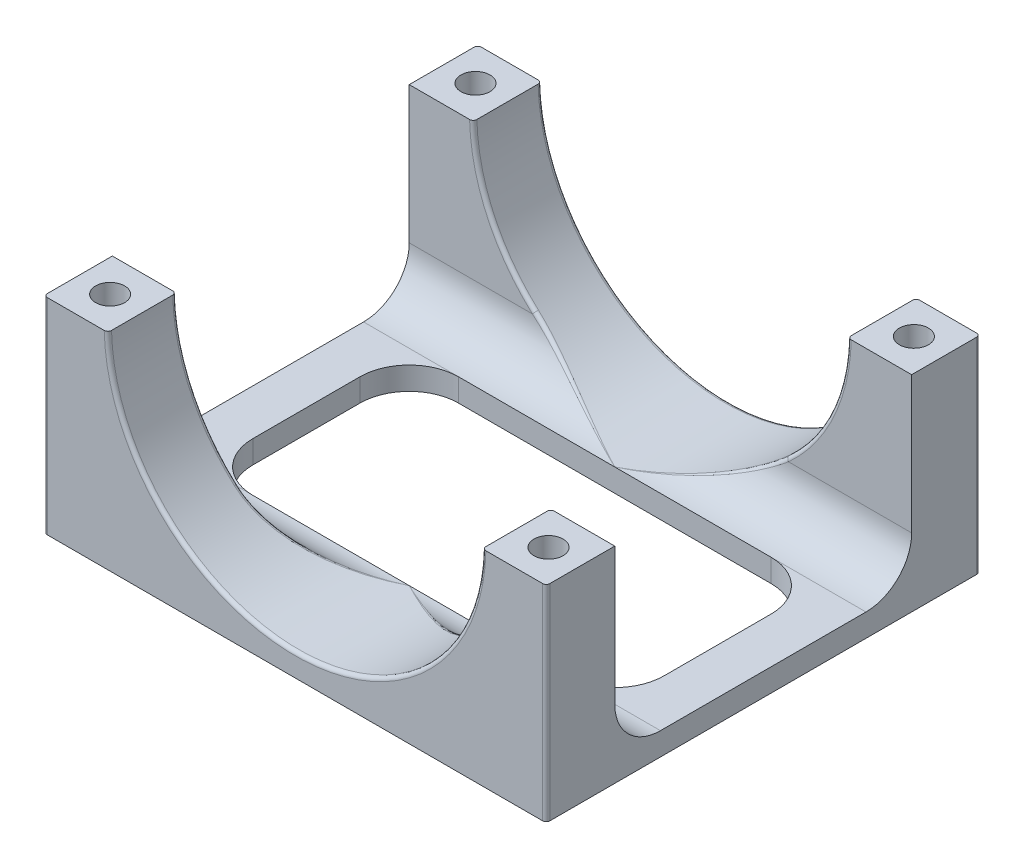
SolidWorks part; units mm, degrees
material "6061-T6 (SS)"
ref_plane "Front Plane" through (0, 0, 0) normal (0, 0, 1) x (1, 0, 0)
ref_plane "Top Plane" through (0, 0, 0) normal (0, 1, 0) x (1, 0, 0)
ref_plane "Right Plane" through (0, 0, 0) normal (1, 0, 0) x (0, 0, -1)
sketch "Sketch1" plane through (0, 0, 0) normal (0, 0, 1) x (1, 0, 0)
  line L0 (-1000, 0) -> (49000, 0) construction
  line L1 (-34.925, -0.635) -> (-26.0273, -0.635)
  line L2 (-34.925, -0.635) -> (-34.925, -29.21)
  line L3 (-34.925, -29.21) -> (34.925, -29.21)
  line L4 (34.925, -29.21) -> (34.925, -0.635)
  line L5 (34.925, -0.635) -> (26.0273, -0.635)
  arc A0 (-26.0273, -0.635) -> (26.0273, -0.635) centre (0, 0) ccw
  dimension "D1" = 52.07
  dimension "D2" = 1.27
  dimension "D3" = 69.85
  dimension "D4" = 3.175
extrude "Boss-Extrude1" add sketch "Sketch1" along normal mid plane 60.325
sketch "Sketch3" plane through (34.925, 0, 0) normal (1, 0, 0) x (0, 0, -1)
  line L0 (-30.1625, -29.21) -> (30.1625, -29.21) construction
  line L1 (-20.6375, 26.035) -> (20.6375, 26.035)
  line L2 (-20.6375, 26.035) -> (-20.6375, -19.685)
  line L3 (-14.2875, -26.035) -> (14.2875, -26.035)
  line L4 (20.6375, 26.035) -> (20.6375, -19.685)
  line L5 (-20.6375, 26.035) -> (20.6375, -26.035) construction
  line L6 (-20.6375, -26.035) -> (20.6375, 26.035) construction
  line L7 (30.1625, -29.21) -> (30.1625, -0.635) construction
  arc A0 (-20.6375, -19.685) -> (-14.2875, -26.035) centre (-14.2875, -19.685) ccw
  arc A1 (14.2875, -26.035) -> (20.6375, -19.685) centre (14.2875, -19.685) ccw
  point P0 (0, 0)
  dimension "D3" = 6.35
  dimension "D1" = 3.175
  dimension "D2" = 9.525
extrude "Cut-Extrude2" cut sketch "Sketch3" against normal through all
sketch "Sketch4" plane through (0, -26.035, 0) normal (0, 1, 0) x (1, 0, 0)
  line L0 (-34.925, 14.2875) -> (0, 14.2875) construction
  line L1 (-28.575, 14.2875) -> (28.575, 14.2875)
  line L2 (-28.575, 14.2875) -> (-28.575, -14.2875)
  line L3 (-28.575, -14.2875) -> (28.575, -14.2875)
  line L4 (28.575, 14.2875) -> (28.575, -14.2875)
  line L5 (-28.575, 14.2875) -> (28.575, -14.2875) construction
  line L6 (-28.575, -14.2875) -> (28.575, 14.2875) construction
  line L7 (-34.925, -14.2875) -> (-34.925, 14.2875) construction
  point P0 (0, 0)
  dimension "D1" = 6.35
extrude "Cut-Extrude3" cut sketch "Sketch4" against normal through all
fillet "Fillet1" radius 6.858 4 edges at (-28.575, -27.6225, 14.2875) (28.575, -27.6225, 14.2875) (28.575, -27.6225, -14.2875) (-28.575, -27.6225, -14.2875)
hole_wizard "#10-32 Tapped Hole1" positions "Sketch5" profile "Sketch6" tap size "#10-32" standard "ANSI Inch" end condition through all
sketch "Sketch5" plane through (0, -0.635, 0) normal (0, 1, 0) x (1, 0, 0)
  line L0 (-30.4761, 25.4) -> (30.4761, -25.4)
  line L3 (30.4761, 25.4) -> (-30.4761, -25.4)
  line L5 (-34.925, -25.4) -> (-26.0273, -25.4)
  line L6 (-34.925, -30.1625) -> (-34.925, -20.6375) construction
  line L7 (-26.0273, -30.1625) -> (-26.0273, -20.6375) construction
  point P0 (-30.4761, 25.4)
  point P2 (-30.4761, -25.4)
  point P4 (30.4761, 25.4)
  point P6 (30.4761, -25.4)
  dimension "D1" = 50.8
sketch "Sketch6" plane through (-30.4761, -0.635, -25.4) normal (1, 0, 0) x (0, 0, 1)
  line L0 (0, 0) -> (0, 28.575)
  line L1 (0, 28.575) -> (2.0193, 28.575)
  line L2 (2.0193, 28.575) -> (2.0193, 0)
  line L5 (2.0193, 0) -> (0, 0)
  line L11 (0, -6.35) -> (0, 107.95) construction
  dimension "Thru Tap Drill Dia." = 4.0386
  dimension "Thru Tap Drill Depth" = 28.575
cosmetic thread "Hole Thread1" parameters "D2"=4.826
cosmetic thread "Hole Thread2" parameters "D2"=4.826
cosmetic thread "Hole Thread3" parameters "D2"=4.826
cosmetic thread "Hole Thread4" parameters "D2"=4.826
fillet "Fillet2" radius 0.508 4 edges at (-34.925, -14.9225, -30.1625) (34.925, -14.9225, -30.1625) (34.925, -14.9225, 30.1625) (-34.925, -14.9225, 30.1625)
sketch "Sketch7" plane through (0, 0, -20.6375) normal (0, 0, 1) x (1, 0, 0)
  line L0 (-34.925, -19.685) -> (34.925, -19.685)
sketch "Sketch8" plane through (0, 0, 20.6375) normal (0, 0, -1) x (-1, 0, 0)
  line L0 (-34.925, -19.685) -> (34.925, -19.685)
fillet "Fillet3" radius 0.508 10 edges at (23.5457, -11.1096, -20.6375) (-12.9882, -22.5639, -19.9474) (12.9882, -22.5639, -19.9474) (23.5457, -11.1096, 20.6375) (-12.9882, -22.5639, 19.9474) (12.9882, -22.5639, 19.9474) (0, -26.035, -30.1625) (-23.5457, -11.1096, -20.6375) (-23.5457, -11.1096, 20.6375) (0, -26.035, 30.1625)
